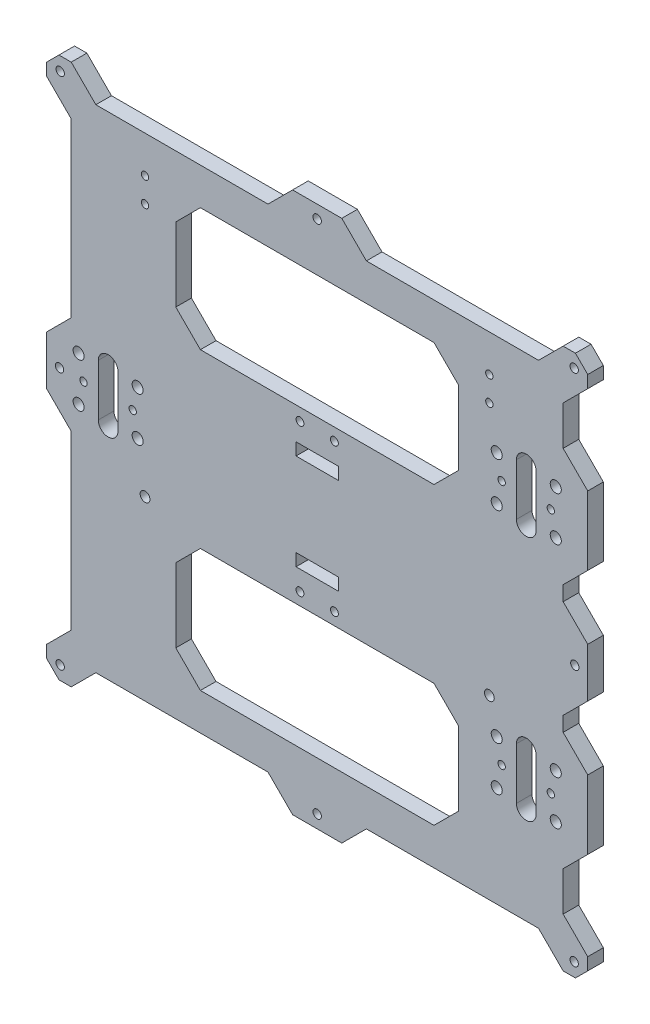
SolidWorks part; units mm, degrees
ref_plane "Front" through (0, 0, 0) normal (0, 0, 1) x (1, 0, 0)
ref_plane "Top" through (0, 0, 0) normal (0, 1, 0) x (1, 0, 0)
ref_plane "Right" through (0, 0, 0) normal (1, 0, 0) x (0, 0, -1)
sketch "Model" plane through (0, 0, 0) normal (0, 0, 1) x (1, 0, 0)
  line L0 (-81, -10.5) -> (-81, 10.5)
  line L1 (-89, 10.5) -> (-89, -10.5)
  line L2 (89, 39.5) -> (89, 60.5)
  line L3 (81, 60.5) -> (81, 39.5)
  line L4 (89, -60.5) -> (89, -39.5)
  line L5 (81, -39.5) -> (81, -60.5)
  line L6 (110, -105) -> (110, -100)
  line L7 (105, -110) -> (110, -105)
  line L8 (100, -110) -> (105, -110)
  line L9 (100, -110) -> (90, -100)
  line L10 (90, -100) -> (20, -100)
  line L11 (20, -100) -> (10, -110)
  line L12 (-10, -110) -> (10, -110)
  line L13 (-10, -110) -> (-20, -100)
  line L14 (-20, -100) -> (-90, -100)
  line L15 (-90, -100) -> (-100, -110)
  line L16 (-105, -110) -> (-100, -110)
  line L17 (-110, -105) -> (-105, -110)
  line L18 (-110, -100) -> (-110, -105)
  line L19 (-110, -100) -> (-100, -90)
  line L20 (-100, -90) -> (-100, -20)
  line L21 (-100, -20) -> (-110, -10)
  line L22 (-110, 10) -> (-110, -10)
  line L23 (-110, 10) -> (-100, 20)
  line L24 (-100, 20) -> (-100, 90)
  line L25 (-100, 90) -> (-110, 100)
  line L26 (-110, 105) -> (-110, 100)
  line L27 (-105, 110) -> (-110, 105)
  line L28 (-100, 110) -> (-105, 110)
  line L29 (-100, 110) -> (-90, 100)
  line L30 (-90, 100) -> (-20, 100)
  line L31 (-20, 100) -> (-10, 110)
  line L32 (10, 110) -> (-10, 110)
  line L33 (10, 110) -> (20, 100)
  line L34 (20, 100) -> (90, 100)
  line L35 (90, 100) -> (100, 110)
  line L36 (105, 110) -> (100, 110)
  line L37 (110, 105) -> (105, 110)
  line L38 (110, 100) -> (110, 105)
  line L39 (110, 100) -> (100, 90)
  line L40 (100, 90) -> (100, 74)
  line L41 (100, 74) -> (110, 64)
  line L42 (110, 36) -> (110, 64)
  line L43 (110, 36) -> (100, 26)
  line L44 (100, 26) -> (100, 20)
  line L45 (100, 20) -> (110, 10)
  line L46 (110, -10) -> (110, 10)
  line L47 (110, -10) -> (100, -20)
  line L48 (100, -20) -> (100, -26)
  line L49 (100, -26) -> (110, -36)
  line L50 (110, -64) -> (110, -36)
  line L51 (110, -64) -> (100, -74)
  line L52 (100, -74) -> (100, -90)
  line L53 (100, -90) -> (110, -100)
  line L54 (-47.4897, 85) -> (-57.4897, 75)
  line L55 (-57.4897, 75) -> (-57.4897, 45)
  line L56 (-57.4897, 45) -> (-47.4897, 35)
  line L57 (-47.4897, 35) -> (47.4897, 35)
  line L58 (47.4897, 35) -> (57.4897, 45)
  line L59 (57.4897, 45) -> (57.4897, 75)
  line L60 (57.4897, 75) -> (47.4897, 85)
  line L61 (47.4897, 85) -> (-47.4897, 85)
  line L62 (57.4897, -45) -> (47.4897, -35)
  line L63 (47.4897, -35) -> (-47.4897, -35)
  line L64 (-47.4897, -35) -> (-57.4897, -45)
  line L65 (-57.4897, -45) -> (-57.4897, -75)
  line L66 (-57.4897, -75) -> (-47.4897, -85)
  line L67 (-47.4897, -85) -> (47.4897, -85)
  line L68 (47.4897, -85) -> (57.4897, -75)
  line L69 (57.4897, -75) -> (57.4897, -45)
  line L70 (-8.6, 22) -> (-8.6, 17)
  line L71 (-8.6, 17) -> (8.6, 17)
  line L72 (8.6, 17) -> (8.6, 22)
  line L73 (8.6, 22) -> (-8.6, 22)
  line L74 (-8.6, -22) -> (-8.6, -17)
  line L75 (-8.6, -17) -> (8.6, -17)
  line L76 (8.6, -17) -> (8.6, -22)
  line L77 (8.6, -22) -> (-8.6, -22)
  circle A0 centre (0, -104.75) radius 1.7
  circle A1 centre (104.75, 0) radius 1.7
  circle A2 centre (104.5, 104.5) radius 1.7
  circle A3 centre (104.5, -104.5) radius 1.7
  circle A4 centre (-95, 0) radius 1.5
  circle A5 centre (-75, 0) radius 1.5
  circle A6 centre (-73, 9) radius 2.25
  circle A7 centre (-73, -9) radius 2.25
  circle A8 centre (-97, -9) radius 2.25
  circle A9 centre (-97, 9) radius 2.25
  circle A10 centre (75, 50) radius 1.5
  circle A11 centre (95, 50) radius 1.5
  circle A12 centre (75, -50) radius 1.5
  circle A13 centre (95, -50) radius 1.5
  circle A14 centre (97, 59) radius 2.25
  circle A15 centre (97, 41) radius 2.25
  circle A16 centre (73, 41) radius 2.25
  circle A17 centre (73, 59) radius 2.25
  circle A18 centre (97, -41) radius 2.25
  circle A19 centre (97, -59) radius 2.25
  circle A20 centre (73, -59) radius 2.25
  circle A21 centre (73, -41) radius 2.25
  circle A22 centre (-104.75, 0) radius 1.7
  circle A23 centre (0, 104.75) radius 1.7
  circle A24 centre (-104.5, 104.5) radius 1.7
  circle A25 centre (-104.5, -104.5) radius 1.7
  arc A26 (-81, 10.5) -> (-89, 10.5) centre (-85, 10.5) ccw
  arc A27 (-89, -10.5) -> (-81, -10.5) centre (-85, -10.5) ccw
  arc A28 (89, 60.5) -> (81, 60.5) centre (85, 60.5) ccw
  arc A29 (81, 39.5) -> (89, 39.5) centre (85, 39.5) ccw
  arc A30 (89, -39.5) -> (81, -39.5) centre (85, -39.5) ccw
  arc A31 (81, -60.5) -> (89, -60.5) centre (85, -60.5) ccw
  circle A32 centre (-7, 30) radius 1.6
  circle A33 centre (7, 30) radius 1.6
  circle A34 centre (-7, -30) radius 1.6
  circle A35 centre (7, -30) radius 1.6
  circle A40 centre (70, -28) radius 2
  circle A41 centre (-70, -28) radius 2
  circle A42 centre (-70, 85) radius 1.5
  circle A43 centre (-70, 75) radius 1.5
  circle A44 centre (70, 85) radius 1.5
  circle A45 centre (70, 75) radius 1.5
extrude "Boss-Extrude1" add sketch "Model" along normal blind 6.35 contours L30 L31 L32 L33 L34 L35 L36 L37 L38 L39 L40 L41 L42 L43 L44 L45 L46 L47 L48 L49 L50 L51 L52 L53 L6 L7 L8 L9 L10 L11 L12 L13 L14 L15 L16 L17 L18 L19 L20 L21 L22 L23 L24 L25 L26 L27 L28 L29
extrude "Cut-Extrude1" cut sketch "Model<4>" along normal blind 6.35 contours L57 L58 L59 L60 L61 L54 L55 L56
sketch "Model<4>" plane through (0, 0, 0) normal (0, 0, 1) x (1, 0, 0) same geometry as "Model"
extrude "Cut-Extrude2" cut sketch "Model<5>" along normal blind 6.35 contours L63 L64 L65 L66 L67 L68 L69 L62
sketch "Model<5>" plane through (0, 0, 0) normal (0, 0, 1) x (1, 0, 0) same geometry as "Model"
extrude "Cut-Extrude3" cut sketch "Model<7>" along normal blind 6.35 contours A0 | A1 | A2 | A8 | A4 | A9 | A6 | A5 | A7 | A3 | A16 | A10 | A17 | A14 | A11 | A15 | A13 | A12 | A24 | A23 | A22 | A25 | A18 | A19 | A20 | A21 | A32 | A33 | A34 | A35 | A43 | A42 | A44 | A45 | A41 | A40
sketch "Model<7>" plane through (0, 0, 0) normal (0, 0, 1) x (1, 0, 0) same geometry as "Model"
extrude "Cut-Extrude4" cut sketch "Model<8>" along normal blind 6.35 contours A27 L0 A26 L1 | L5 A31 L4 A30 | A28 L3 A29 L2 | L70 L71 L72 L73 | L75 L76 L77 L74
sketch "Model<8>" plane through (0, 0, 0) normal (0, 0, 1) x (1, 0, 0) same geometry as "Model"
